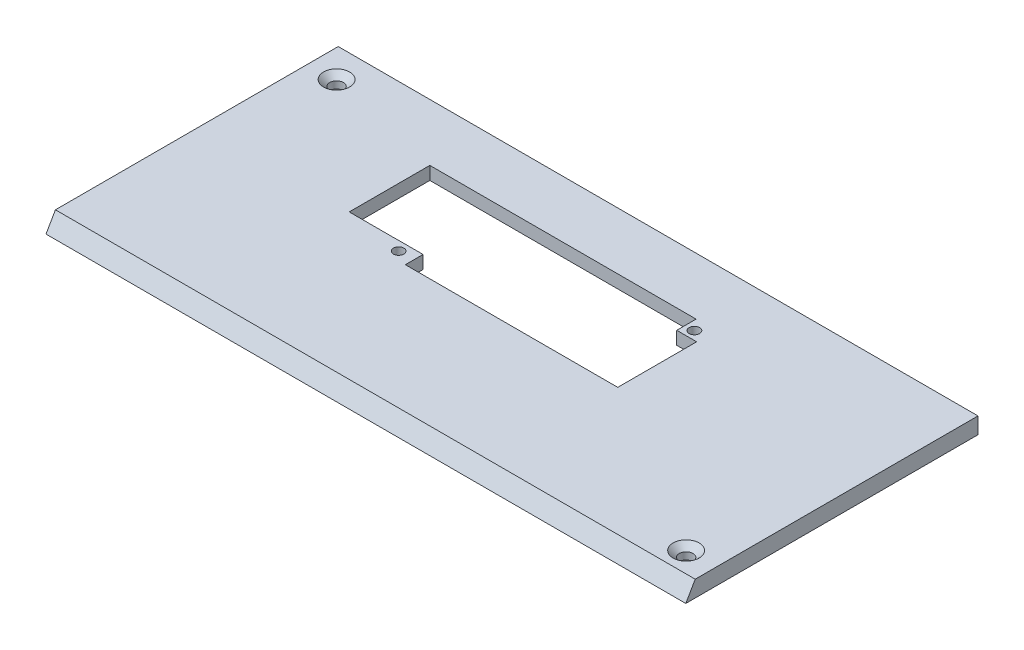
SolidWorks part; units mm, degrees
ref_plane "Alzado" through (0, 0, 0) normal (0, 0, 1) x (1, 0, 0)
ref_plane "Planta" through (0, 0, 0) normal (0, 1, 0) x (1, 0, 0)
ref_plane "Vista lateral" through (0, 0, 0) normal (1, 0, 0) x (0, 0, -1)
sketch "Croquis1" plane through (0, 0, 0) normal (1, 0, 0) x (0, 0, -1)
  line L0 (0, 0) -> (89.52, 0)
  line L1 (89.52, 0) -> (89.52, 5)
  line L2 (89.52, 5) -> (2.8868, 5)
  line L3 (0, 0) -> (2.8868, 5)
  dimension "D1" = 89.52
  dimension "D2" = 5
  dimension "D3" = 120
extrude "Saliente-Extruir1" add sketch "Croquis1" along normal blind 196
shell "Vaciado1" thickness 4 removed face at (98, 0, -44.76)
sketch "Sketch2" plane through (0, 1, 0) normal (0, -1, 0) x (-1, 0, 0)
  line L0 (-59.6372, 47.3551) -> (-68.1615, 47.3551)
  line L5 (-68.1615, 47.3551) -> (-68.1615, 41.923)
  line L6 (-68.1615, 41.923) -> (-133.2369, 41.923)
  line L7 (-133.2369, 41.923) -> (-133.2369, 66.0933)
  line L8 (-133.2369, 66.0933) -> (-127.1352, 66.0933)
  line L9 (-127.1352, 66.0933) -> (-127.1352, 72.023)
  line L10 (-127.1352, 72.023) -> (-59.6372, 72.023)
  line L12 (-59.6372, 72.023) -> (-59.6372, 47.3551)
  circle A0 centre (-63.5269, 44.5067) radius 1.6
  circle A1 centre (-129.9169, 68.723) radius 1.6
  point P4 (-97.9669, 56.973)
sketch "Sketch4" plane through (0, 1, 0) normal (0, -1, 0) x (-1, 0, 0)
  circle A0 centre (-8.5, 80.52) radius 1.585
  circle A1 centre (-187, 9.1109) radius 1.585
extrude "Cut-Extrude3" cut sketch "Sketch4" against normal blind 13
hole_wizard "Avellanado para tornillo con cabeza avellanada en cruz de M3.51" positions "3DSketch1" profile "Sketch5" countersink size "M3.5" standard "AS"
sketch3d "3DSketch1"
  line L0 (187, 5, -9.1109) -> (187, 1, -9.1109) construction
  line L1 (8.5, 5, -80.52) -> (8.5, 1, -80.52) construction
  point P0 (187, 5, -9.1109)
  point P4 (8.5, 5, -80.52)
sketch "Sketch5" plane through (187, 5, -9.1109) normal (1, 0, 0) x (0, 0, 1)
  line L0 (0, 0) -> (0, 11.2618)
  line L1 (0, 11.2618) -> (2.1, 10)
  line L2 (2.1, 10) -> (2.1, 1.8348)
  line L3 (2.1, 1.8348) -> (4, 0)
  line L5 (4, 0) -> (0, 0)
  line L6 (-2.1, 1.8348) -> (-4, 0) construction
  line L10 (0, 11.2618) -> (-2.1, 10) construction
  line L11 (0, -6.35) -> (0, 107.95) construction
  dimension "Diámetro de taladro" = 4.2
  dimension "Profundidad de taladro" = 10
  dimension "Ángulo de avellanado cercano" = 8
  dimension "Ángulo de avellanado lejano" = 92
  dimension "Ángulo de perforador" = 118
extrude "Cut-Extrude4" cut sketch "Sketch2" against normal blind 10
sketch "Sketch6" plane through (0, 5, 0) normal (0, 1, 0) x (1, 0, 0)
  line L1 (59.6372, 72.023) -> (45.5649, 72.023)
  line L2 (59.6372, 72.023) -> (59.6372, 47.3297)
  line L3 (59.6372, 47.3297) -> (45.5649, 47.3297)
  line L4 (45.5649, 72.023) -> (45.5649, 47.3297)
  line L5 (59.6372, 72.023) -> (45.5649, 47.3297) construction
  line L6 (59.6372, 47.3297) -> (45.5649, 72.023) construction
  point P4 (52.601, 59.6763)
extrude "Cut-Extrude5" cut sketch "Sketch6" against normal blind 10
